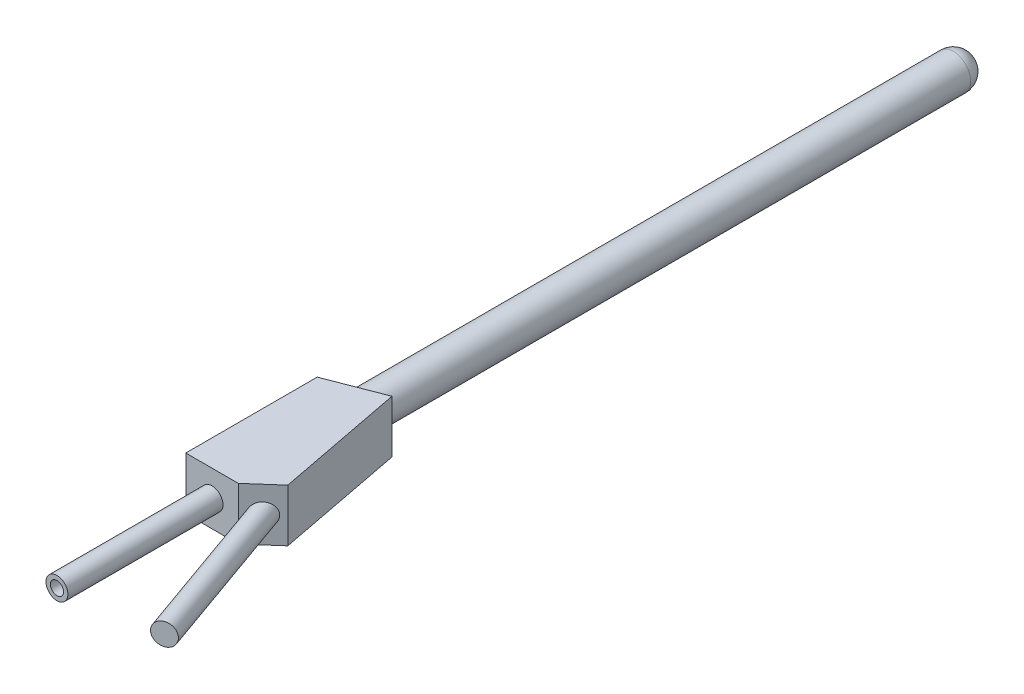
SolidWorks part; units mm, degrees
ref_plane "Front Plane" through (0, 0, 0) normal (0, 0, 1) x (1, 0, 0)
ref_plane "Top Plane" through (0, 0, 0) normal (0, 1, 0) x (1, 0, 0)
ref_plane "Right Plane" through (0, 0, 0) normal (1, 0, 0) x (0, 0, -1)
sketch "Sketch1" plane through (0, 0, 0) normal (0, 1, 0) x (1, 0, 0)
  line L0 (0, 0) -> (6.1582, 2.3741)
  line L1 (6.1582, 2.3741) -> (9, -12.3542)
  line L2 (9, -12.3542) -> (6, -15)
  line L3 (6, -15) -> (0, -15)
  line L4 (0, -15) -> (0, 0)
  dimension "D1" = 15
  dimension "D2" = 6.6
  dimension "D3" = 15
  dimension "D4" = 6
  dimension "D5" = 9
  dimension "D6" = 4
extrude "Boss-Extrude1" add sketch "Sketch1" along normal blind 6
sketch "Sketch4" plane through (0, 0, 0) normal (0, 0, 1) x (1, 0, 0)
  line L0 (0, 0) -> (6.1582, 6) construction
  line L1 (0, 6) -> (6.1582, 0) construction
  circle A0 centre (3.0791, 3) radius 2
  point P10 (3.0791, 3)
  dimension "D1" = 4
extrude "Boss-Extrude2" add sketch "Sketch4" against normal blind 71.5
fillet "Fillet1" radius 2 1 edges at (5.0791, 3, -71.5)
sketch "Sketch5" plane through (0, 0, 15) normal (0, 0, 1) x (1, 0, 0)
  line L0 (0, 0) -> (6, 0) construction
  line L1 (0, 6) -> (0, 0) construction
  circle A0 centre (3, 3) radius 1.25
  dimension "D1" = 2.5
  dimension "D2" = 3
  dimension "D3" = 3
extrude "Boss-Extrude3" add sketch "Sketch5" along normal blind 17.7
shell "Shell1" thickness 0.5 removed face at (4.25, 3, 32.7)
sketch "Sketch6" plane through (0, 6, 0) normal (0, 1, 0) x (1, 0, 0)
  line L0 (2.3298, 0.8982) -> (7.5, -13.6771) construction
  line L1 (6, -15) -> (9, -12.3542) construction
  line L2 (6.1582, 2.3741) -> (0, 0) construction
ref_plane "Plane1" through (7.5, 6, 13.6771) normal (0.3343, 0, 0.9425) x (0.9425, 0, -0.3343)
sketch "Sketch7" plane through (7.5, 6, 13.6771) normal (0.3343, 0, 0.9425) x (0.9425, 0, -0.3343)
  line L0 (1.8559, 0) -> (1.8559, -6) construction
  line L2 (-1.8559, -6) -> (1.8559, -6) construction
  circle A0 centre (0.0009, -3) radius 1.25
  dimension "D1" = 2.5
  dimension "D2" = 1.855
  dimension "D3" = 3
extrude "Boss-Extrude4" add sketch "Sketch7" along normal blind 18.5
extrude "Boss-Extrude5" add sketch "Sketch7<2>" against normal blind 5
sketch "Sketch7<2>" plane through (7.5, 6, 13.6771) normal (0.3343, 0, 0.9425) x (0.9425, 0, -0.3343) same geometry as "Sketch7"
